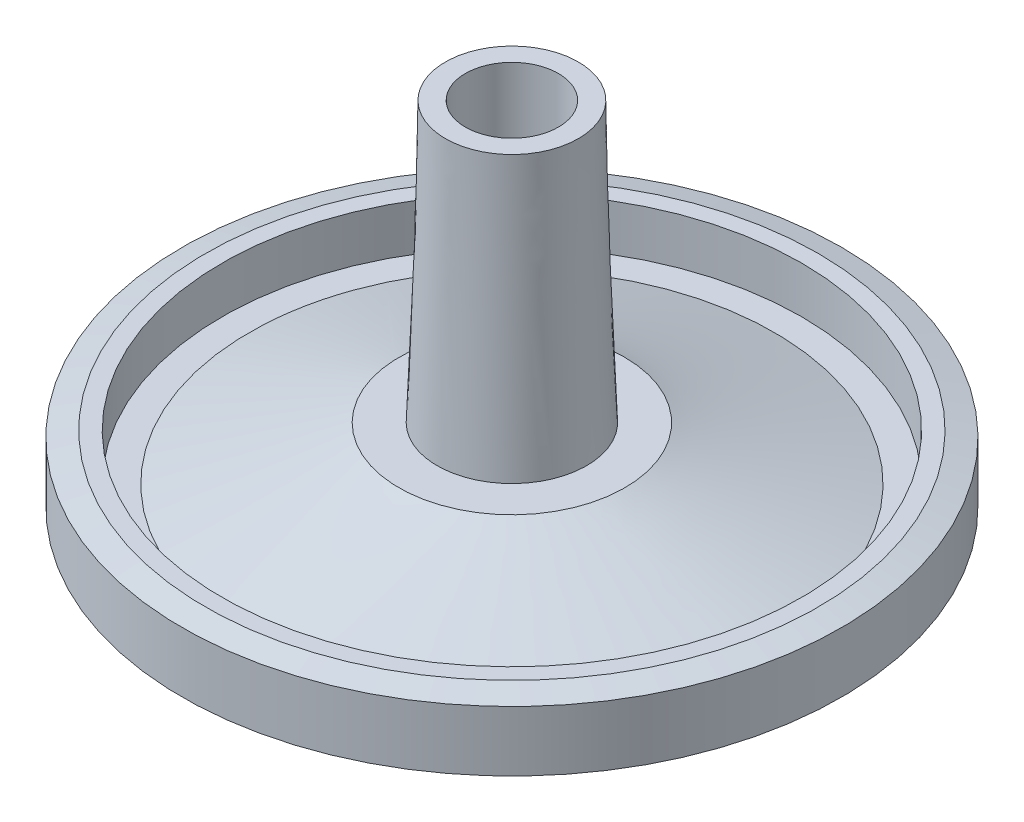
SolidWorks part; units mm, degrees
ref_plane "Front Plane" through (0, 0, 0) normal (0, 0, 1) x (1, 0, 0)
ref_plane "Top Plane" through (0, 0, 0) normal (0, 1, 0) x (1, 0, 0)
ref_plane "Right Plane" through (0, 0, 0) normal (1, 0, 0) x (0, 0, -1)
sketch "Sketch1" plane through (0, 0, 0) normal (0, 1, 0) x (1, 0, 0)
  circle A0 centre (0, 0) radius 5
  dimension "D1" = 10
ref_plane "Plane1" through (0, -21, 0) normal (0, 1, 0) x (1, 0, 0)
sketch "Sketch2" plane through (0, -21, 0) normal (0, 1, 0) x (1, 0, 0)
  circle A0 centre (0, 0) radius 5.625
  dimension "D1" = 11.25
loft "Loft1" add profiles "Sketch1", "Sketch2" connector at (-3.0397, 0, -3.97) connector at (-4.7341, -21, -3.0379)
sketch "Sketch3" plane through (0, 0, 0) normal (0, 1, 0) x (1, 0, 0)
  circle A0 centre (0, 0) radius 3.5
  dimension "D1" = 7
extrude "Cut-Extrude1" cut sketch "Sketch3" against normal blind 8.5
sketch "Sketch4" plane through (0, -21, 0) normal (0, -1, 0) x (1, 0, 0)
  circle A0 centre (0, 0) radius 8.5
  dimension "D1" = 17
ref_plane "Plane2" through (0, -25, 0) normal (0, -1, 0) x (-1, 0, 0)
sketch "Sketch5" plane through (0, -25, 0) normal (0, -1, 0) x (-1, 0, 0)
  circle A0 centre (0, 0) radius 19.75
  dimension "D1" = 39.5
loft "Loft2" add profiles "Sketch4", "Sketch5" connector at (-8.4929, -21, 0.347) connector at (-17.8598, -25, -8.4316)
sketch "Sketch6" plane through (0, -25, 0) normal (0, -1, 0) x (1, 0, 0)
  circle A0 centre (0, 0) radius 24.8
  circle A1 centre (0, 0) radius 21.8
  dimension "D1" = 49.6
  dimension "D2" = 3
extrude "Boss-Extrude1" add sketch "Sketch6" against normal blind 3.5 separate body
chamfer "Chamfer1" distance 1.75 angle 15 1 edges at (0, -21.5, -24.8) first distance on face at (0, -21.5, -21.8)
sketch "Sketch7" plane through (0, -25, 0) normal (0, -1, 0) x (1, 0, 0)
  circle A0 centre (0, 0) radius 24.8
extrude "Boss-Extrude2" add sketch "Sketch7" along normal blind 1.5
sketch "Sketch8" plane through (0, -26.5, 0) normal (0, -1, 0) x (1, 0, 0)
  circle A0 centre (0, 0) radius 20.5
  circle A1 centre (0, 0) radius 22.5
  dimension "D1" = 41
  dimension "D2" = 2
extrude "Boss-Extrude3" add sketch "Sketch8" along normal blind 1
sketch "Sketch9" plane through (0, -26.5, 0) normal (0, -1, 0) x (1, 0, 0)
  circle A0 centre (0, 0) radius 19.5
  dimension "D1" = 39
ref_plane "Plane3" through (0, -23.5, 0) normal (0, -1, 0) x (-1, 0, 0)
sketch "Sketch10" plane through (0, -23.5, 0) normal (0, -1, 0) x (-1, 0, 0)
  circle A0 centre (0, 0) radius 9.5
  dimension "D1" = 19
loft "Cut-Loft1" cut profiles "Sketch10", "Sketch9" connector at (-5.4087, -23.5, 7.81) connector at (-13.295, -26.5, 14.2651)
fillet "Fillet1" radius 0.5 4 edges at (0, -27.5, -22.5) (0, -26.5, -22.5) (0, -27.5, -20.5) (0, -26.5, -20.5)
sketch "Sketch11" plane through (0, -23.5, 0) normal (0, -1, 0) x (1, 0, 0)
  circle A0 centre (0, 0) radius 5
  dimension "D1" = 10
ref_plane "Plane4" through (0, -19.5, 0) normal (0, -1, 0) x (-1, 0, 0)
sketch "Sketch12" plane through (0, -19.5, 0) normal (0, -1, 0) x (-1, 0, 0)
  circle A0 centre (0, 0) radius 3.75
  dimension "D1" = 7.5
loft "Cut-Loft2" cut profiles "Sketch11", "Sketch12" connector at (-4.3354, -23.5, -2.4909) connector at (-3.6726, -19.5, 0.7581)
sketch "Sketch13" plane through (0, -23.5, 0) normal (0, -1, 0) x (1, 0, 0)
  circle A0 centre (0, 0) radius 3.75
  dimension "D1" = 7.5
extrude "Cut-Extrude2" cut sketch "Sketch13" against normal blind 13.5
sketch "Sketch14" plane through (0, -10, 0) normal (0, -1, 0) x (1, 0, 0)
  circle A0 centre (0, 0) radius 2.5
  dimension "D1" = 5
extrude "Cut-Extrude4" cut sketch "Sketch14" against normal through all
